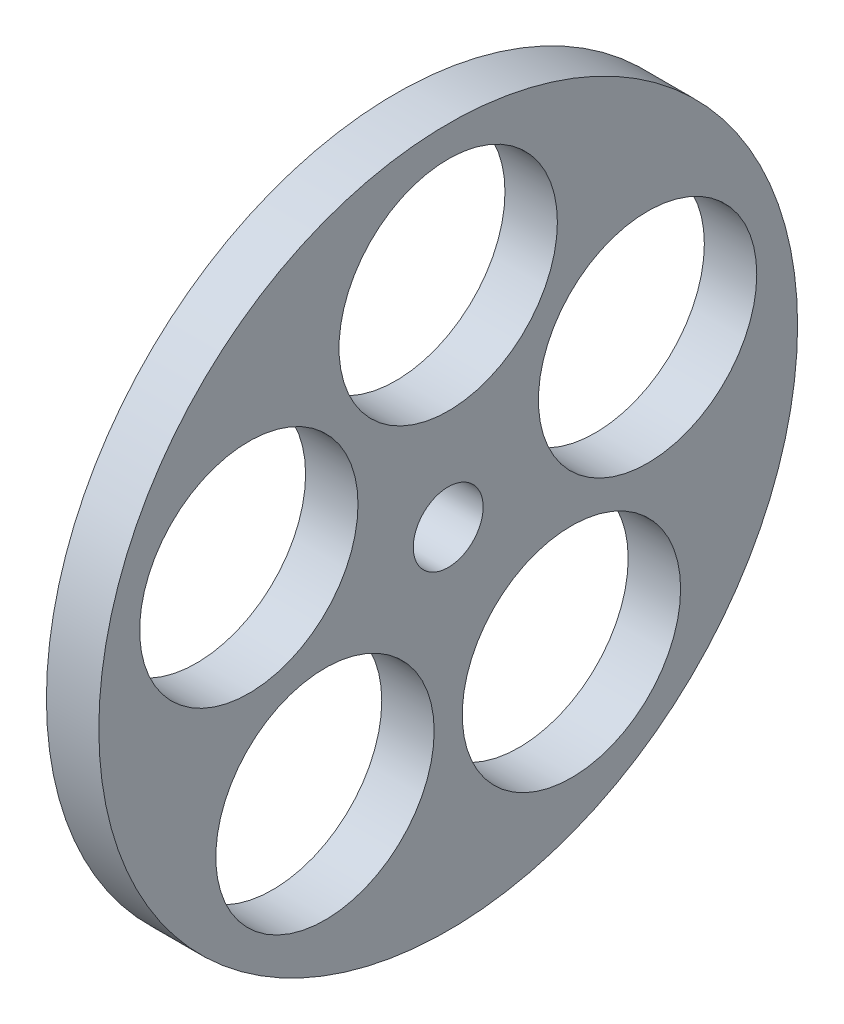
SolidWorks part; units mm, degrees
material "Acrylic (Medium-high impact)"
ref_plane "Front Plane" through (0, 0, 0) normal (0, 0, 1) x (1, 0, 0)
ref_plane "Top Plane" through (0, 0, 0) normal (0, 1, 0) x (1, 0, 0)
ref_plane "Right Plane" through (0, 0, 0) normal (1, 0, 0) x (0, 0, -1)
sketch "Sketch1" plane through (0, 0, 0) normal (1, 0, 0) x (0, 0, -1)
  line L0 (0, 4) -> (0, 40) construction
  circle A0 centre (0, 0) radius 40
  circle A1 centre (0, 0) radius 4
  circle A2 centre (0, 24) radius 12.5
  circle A3 centre (22.8254, 7.4164) radius 12.5
  circle A4 centre (14.1068, -19.4164) radius 12.5
  circle A5 centre (-14.1068, -19.4164) radius 12.5
  circle A6 centre (-22.8254, 7.4164) radius 12.5
  point P18 (0, 0)
  dimension "D1" = 80
  dimension "D2" = 8
  dimension "D3" = 25
  dimension "D5" = 24
  dimension "D4" = 5
extrude "Boss-Extrude1" add sketch "Sketch1" along normal blind 6
